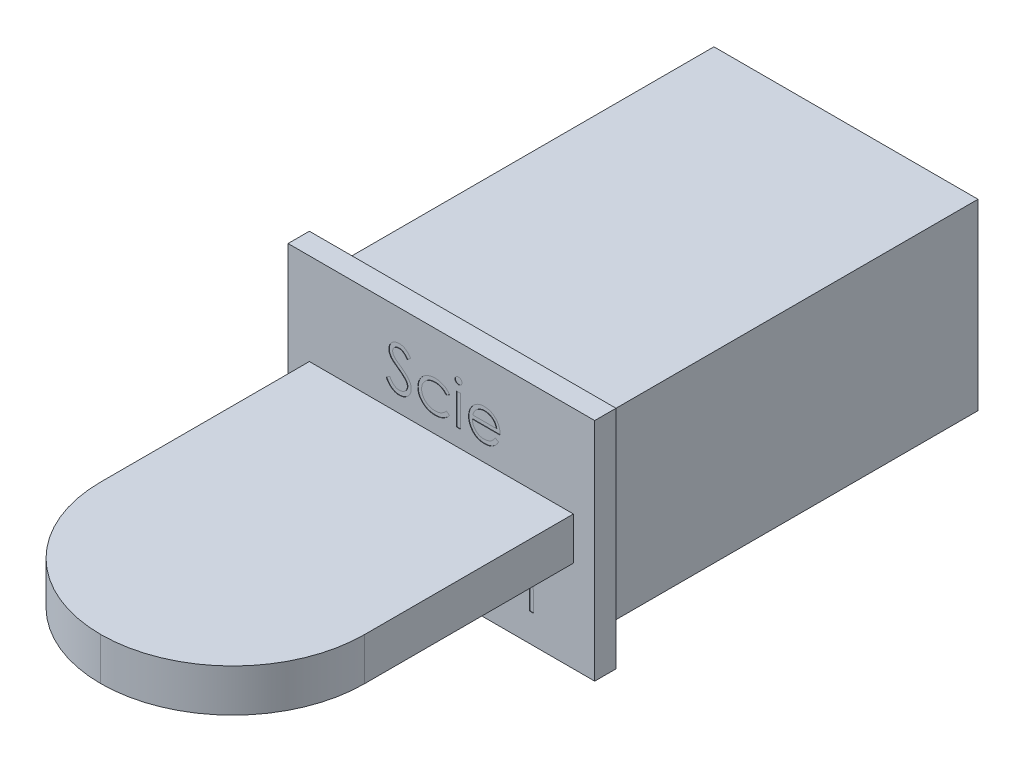
SolidWorks part; units mm, degrees
ref_plane "Front" through (0, 0, 0) normal (0, 0, 1) x (1, 0, 0)
ref_plane "Top" through (0, 0, 0) normal (0, 1, 0) x (1, 0, 0)
ref_plane "Right" through (0, 0, 0) normal (1, 0, 0) x (0, 0, -1)
sketch "Esquisse1" plane through (0, 0, 0) normal (0, 0, 1) x (1, 0, 0)
  line L1 (0, 0) -> (720, 0)
  line L2 (0, 0) -> (0, 530)
  line L3 (0, 530) -> (720, 530)
  line L4 (720, 0) -> (720, 530)
  dimension "D1" = 720
  dimension "D2" = 530
extrude "Boss.-Extru.1" add sketch "Esquisse1" along normal blind 50
sketch "Esquisse2" plane through (0, 0, 0) normal (0, 0, -1) x (-1, 0, 0)
  line L0 (-360, 480) -> (-360, 530) construction
  line L1 (-670, 480) -> (-50, 480)
  line L2 (-670, 480) -> (-670, 50)
  line L3 (-670, 50) -> (-50, 50)
  line L4 (-50, 480) -> (-50, 50)
  line L5 (-720, 530) -> (0, 530) construction
  line L6 (0, 0) -> (-720, 0) construction
  line L9 (-50, 265) -> (0, 265) construction
  line L10 (0, 530) -> (0, 0) construction
  dimension "D1" = 50
extrude "Boss.-Extru.2" add sketch "Esquisse2" along normal blind 900
sketch "Esquisse3" plane through (0, 0, 50) normal (0, 0, 1) x (1, 0, 0)
  line L0 (670, 265) -> (720, 265) construction
  line L1 (50, 215) -> (670, 215)
  line L2 (50, 215) -> (50, 315)
  line L3 (50, 315) -> (670, 315)
  line L4 (670, 215) -> (670, 315)
  line L5 (720, 0) -> (720, 530) construction
  line L6 (360, 215) -> (360, 530) construction
  line L7 (720, 530) -> (0, 530) construction
  dimension "D1" = 50
  dimension "D2" = 100
extrude "Boss.-Extru.3" add sketch "Esquisse3" along normal blind 800
fillet "Congé1" radius 310 2 edges at (670, 265, 850) (50, 265, 850)
sketch "Esquisse4" plane through (0, 0, 50) normal (0, 0, 1) x (1, 0, 0)
  text T0 "Scie" font "Century Gothic" height 100
  text T1 "Ruban" font "Century Gothic" height 100
  point P2 (157.0503, 48.2973)
  point P3 (142.9256, 66.139)
extrude "Enlèv. mat.-Extru.1" cut sketch "Esquisse4" against normal blind 1
